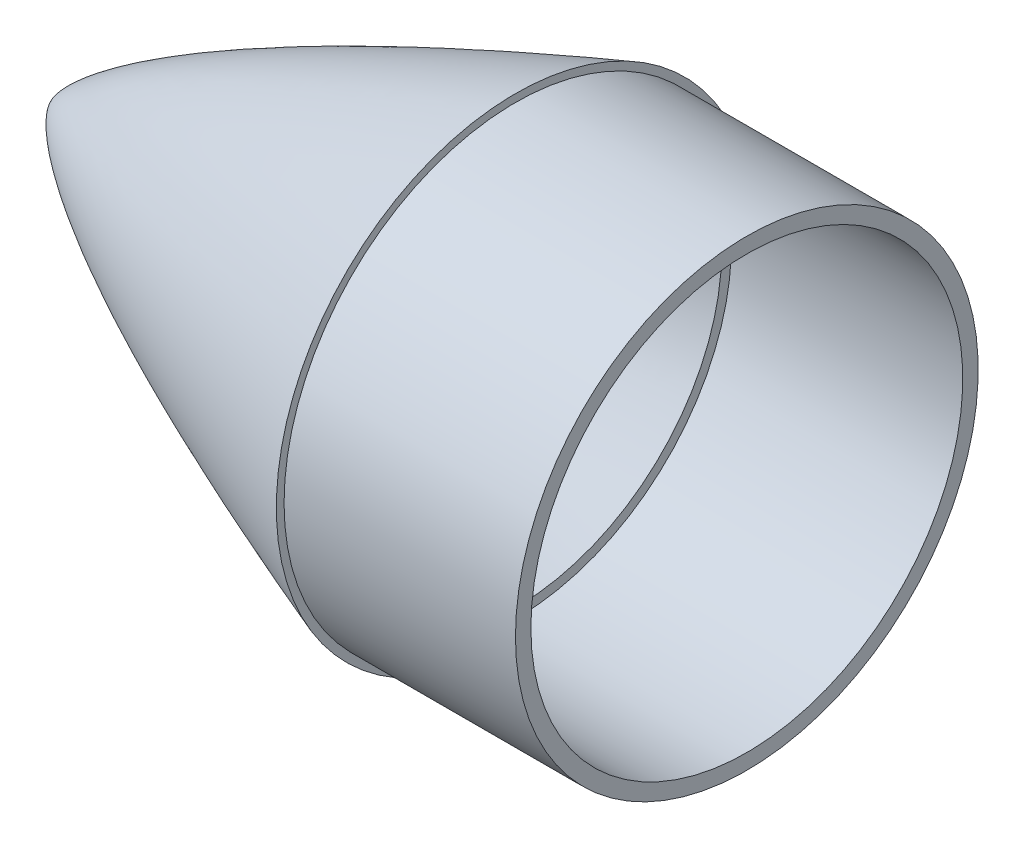
SolidWorks part; units mm, degrees
ref_plane "Front Plane" through (0, 0, 0) normal (0, 0, 1) x (1, 0, 0)
ref_plane "Top Plane" through (0, 0, 0) normal (0, 1, 0) x (1, 0, 0)
ref_plane "Right Plane" through (0, 0, 0) normal (1, 0, 0) x (0, 0, -1)
sketch "Sketch2" plane through (0, 0, 0) normal (0, 1, 0) x (1, 0, 0)
  line L0 (76.2, 39.37) -> (76.2, 0)
  line L1 (76.2, 0) -> (0, 0)
  spline S0 degree 4 poles (0, 0) (0.0015, 0.0206) (0.0063, 0.0615) (0.02, 0.1272) (0.0495, 0.2369) (0.1006, 0.3872) (0.1886, 0.5993) (0.3363, 0.8955) (0.5699, 1.2931) (0.929, 1.8178) (1.4754, 2.5107) (2.2887, 3.4114) (3.4753, 4.5668) (5.1544, 6.0127) (7.489, 7.805) (10.8544, 10.1208) (15.1675, 12.7782) (20.2865, 15.6416) (25.9747, 18.5735) (31.7372, 21.3561) (36.8287, 23.6849) (41.2212, 25.6181) (45.6327, 27.5062) (49.3246, 29.0454) (53.0271, 30.5526) (56.373, 31.8849) (58.6027, 32.7613) (60.4723, 33.4886) (61.9522, 34.0604) (63.4691, 34.6415) (64.9241, 35.1963) (66.4857, 35.7857) (67.8819, 36.3114) (69.9242, 37.0714) (71.8689, 37.7933) (75.2722, 39.0364) (77.7946, 39.9473) (81.3368, 41.2143) (82.674, 41.6815) (83.8832, 42.1091) knots 0 0 0 0 0 0.00087 0.001739 0.002825 0.004788 0.007561 0.011415 0.016771 0.024223 0.034352 0.048601 0.067914 0.094018 0.127748 0.172664 0.240123 0.307582 0.375041 0.442499 0.509958 0.543687 0.577417 0.644876 0.678605 0.712334 0.729199 0.746064 0.762928 0.779793 0.796658 0.813523 0.830387 0.847252 0.880981 0.914711 0.957355 1 1 1 1 1 construction
  spline S1 degree 4 poles (0, 0) (0.0015, 0.0206) (0.0063, 0.0615) (0.02, 0.1272) (0.0495, 0.2369) (0.1006, 0.3872) (0.1886, 0.5993) (0.3363, 0.8955) (0.5699, 1.2931) (0.929, 1.8178) (1.4754, 2.5107) (2.2887, 3.4114) (3.4753, 4.5668) (5.1544, 6.0127) (7.489, 7.805) (10.8544, 10.1208) (15.1675, 12.7782) (20.2865, 15.6416) (25.9747, 18.5735) (31.7372, 21.3561) (36.8287, 23.6849) (41.2212, 25.6181) (45.6327, 27.5062) (49.3246, 29.0454) (53.0271, 30.5526) (56.373, 31.8849) (58.6027, 32.7613) (60.4723, 33.4886) (61.9522, 34.0604) (63.4691, 34.6415) (64.9241, 35.1963) (66.4857, 35.7857) (67.8819, 36.3114) (69.9242, 37.0714) (71.8689, 37.7933) (74.1292, 38.6189) (75.512, 39.1212) (76.2, 39.37) knots 0 0 0 0 0 0.00087 0.001739 0.002825 0.004788 0.007561 0.011415 0.016771 0.024223 0.034352 0.048601 0.067914 0.094018 0.127748 0.172664 0.240123 0.307582 0.375041 0.442499 0.509958 0.543687 0.577417 0.644876 0.678605 0.712334 0.729199 0.746064 0.762928 0.779793 0.796658 0.813523 0.830387 0.847252 0.880981 0.914711 0.914711 0.914711 0.914711 0.914711
revolve "Revolve1" add sketch "Sketch2" angle 360 about L1
shell "Shell1" thickness 5.08 removed face at (76.2, 0, -39.37)
sketch "Sketch3" plane through (76.2, 0, 0) normal (1, 0, 0) x (0, 0, -1)
  circle A0 centre (0, 0) radius 38.1
  dimension "D1" = 76.2
extrude "Extrude-Thin1" add sketch "Sketch3" along normal blind 38.1 thin thin type one direction reverse wall 2.54
